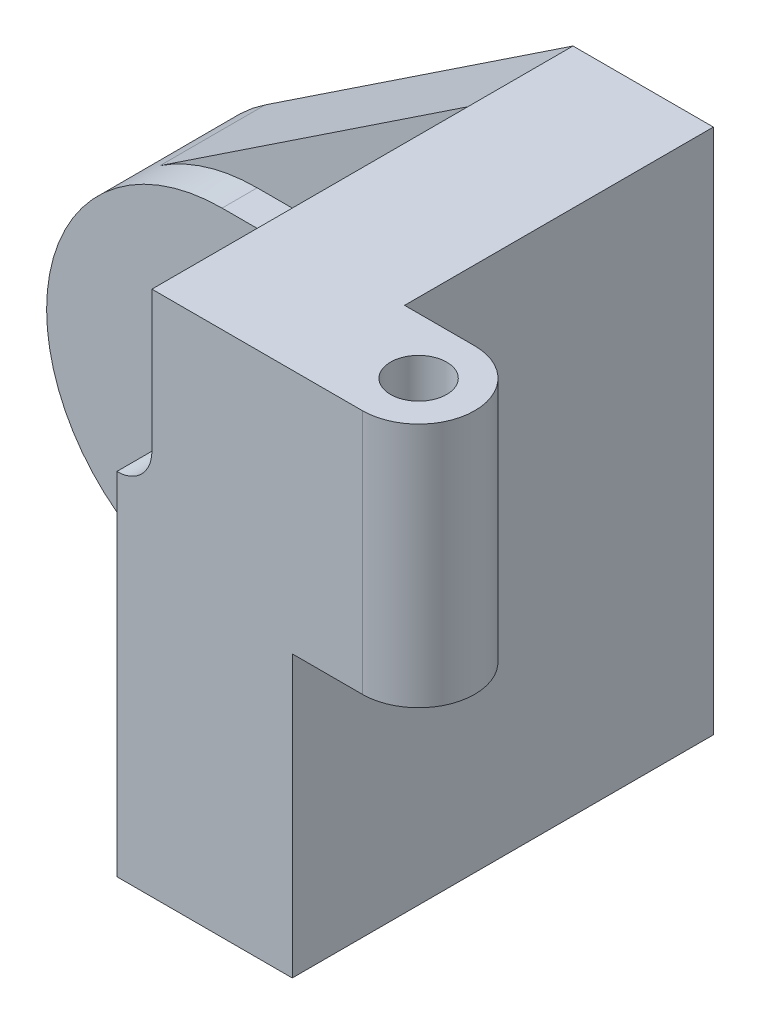
SolidWorks part; units mm, degrees
ref_plane "Front Plane" through (0, 0, 0) normal (0, 0, 1) x (1, 0, 0)
ref_plane "Top Plane" through (0, 0, 0) normal (0, 1, 0) x (1, 0, 0)
ref_plane "Right Plane" through (0, 0, 0) normal (1, 0, 0) x (0, 0, -1)
sketch "Sketch1" plane through (0, 0, 0) normal (0, 0, 1) x (1, 0, 0)
  line L0 (0, 25) -> (25, 25)
  line L1 (25, 25) -> (25, -25)
  line L2 (25, -25) -> (0, -25)
  line L3 (30, 50) -> (30, 30)
  line L4 (30, 50) -> (68, 50)
  line L5 (68, 50) -> (68, 15)
  line L6 (68, 15) -> (50, 15)
  line L7 (50, 15) -> (50, -25)
  line L8 (50, -25) -> (25, -25)
  line L9 (30, 50) -> (-13.8523, 20.8114)
  line L10 (50, 15) -> (50, 50)
  circle A0 centre (0, 0) radius 10
  arc A1 (0, -25) -> (0, 25) centre (0, 0) cw
  arc A2 (25, 25) -> (30, 30) centre (25, 30) ccw
  dimension "D1" = 25
  dimension "D2" = 20
  dimension "D4" = 38
  dimension "D3" = 25
  dimension "D5" = 5
  dimension "D6" = 35
  dimension "D7" = 40
  dimension "D8" = 25
extrude "Boss-Extrude1" add sketch "Sketch1" along normal blind 20 contours A1 L2 L1 L0 A0 | A2 L1 L8 L7 L10 L4 L3 region at (12.5, 24.2929, 0) region at (38.1858, 10.7614, 0)
extrude "Boss-Extrude2" add sketch "Sketch1<3>" along normal blind 40 from surface contours A2 L1 L8 L7 L10 L4 L3 region at (38.1858, 10.7614, 0) starting at face at (23.0051, 18.4235, 20)
sketch "Sketch1<3>" plane through (0, 0, 0) normal (0, 0, 1) x (1, 0, 0) same geometry as "Sketch1"
extrude "Boss-Extrude3" add sketch "Sketch1<4>" along normal blind 15 contours L0 A2 L3 L9 A1 region at (17.0616, 33.3089, 0)
sketch "Sketch1<4>" plane through (0, 0, 0) normal (0, 0, 1) x (1, 0, 0) same geometry as "Sketch1"
sketch "Sketch2" plane through (0, 50, 0) normal (0, 1, 0) x (1, 0, 0)
  line L0 (50, -44) -> (60, -44)
  line L1 (50, -60) -> (50, 0) construction
  line L2 (50, -60) -> (60, -60)
  line L3 (30, -60) -> (30, -15) construction
  arc A0 (60, -44) -> (60, -60) centre (60, -52) cw
  circle A1 centre (60, -52) radius 4
  line M5 (50, -60) -> (50, 0)
  dimension "D1" = 8
  dimension "D3" = 8
  dimension "D2" = 30
extrude "Boss-Extrude4" add sketch "Sketch2" against normal blind 35 contours A0 L0 L2 A1 M5 region at (55, 50, 44.2408)
